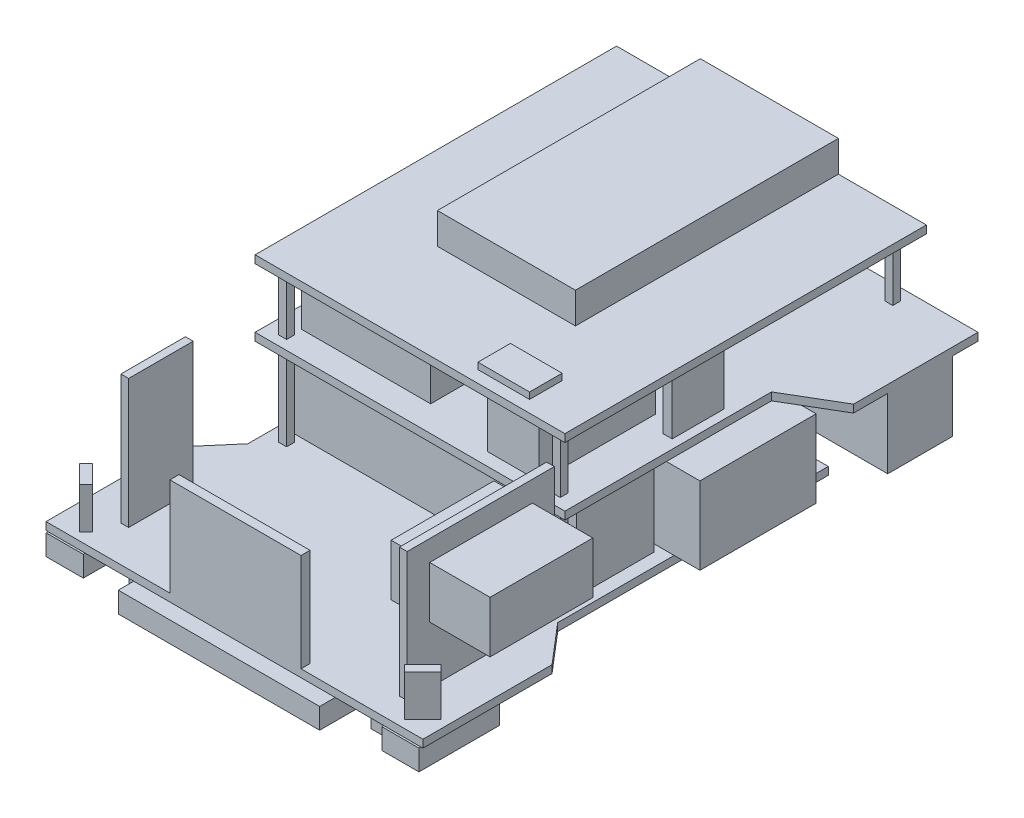
SolidWorks part; units mm, degrees
ref_plane "Front Plane" through (0, 0, 0) normal (0, 0, 1) x (1, 0, 0)
ref_plane "Top Plane" through (0, 0, 0) normal (0, 1, 0) x (1, 0, 0)
ref_plane "Right Plane" through (0, 0, 0) normal (1, 0, 0) x (0, 0, -1)
sketch "Sketch1" plane through (0, 0, 0) normal (0, 1, 0) x (1, 0, 0)
  line L0 (-73, -35) -> (-60, -19.8013)
  line L1 (60, -85) -> (-60, -85)
  line L2 (60, -19.8013) -> (60, 85)
  line L3 (60, 85) -> (-60, 85)
  line L4 (-60, -19.8013) -> (-60, 85)
  line L5 (60, -85) -> (-60, 85) construction
  line L6 (60, 85) -> (-60, -85) construction
  line L7 (0, 0) -> (0, -85) construction
  line L9 (-60, -85) -> (-73, -85)
  line L10 (-73, -35) -> (-73, -85)
  line L11 (60, -85) -> (73, -85)
  line L12 (73, -35) -> (73, -85)
  line L13 (73, -35) -> (60, -19.8013)
  point P0 (0, 0)
  dimension "D1" = 170
  dimension "D2" = 120
  dimension "D3" = 50
  dimension "D4" = 13
  dimension "D5" = 20
extrude "Boss-Extrude1" add sketch "Sketch1" along normal blind 3
sketch "Sketch2" plane through (0, 3, 0) normal (0, 1, 0) x (1, 0, 0)
  line L0 (0, 0) -> (0, 85) construction
  line L1 (60, 85) -> (-60, 85) construction
  line L2 (-60, 85) -> (-60, -19.8013) construction
  line L4 (-54.525, -13.335) -> (-51.475, -13.335)
  line L5 (-54.525, -13.335) -> (-54.525, -10.285)
  line L6 (-54.525, -10.285) -> (-51.475, -10.285)
  line L7 (-51.475, -13.335) -> (-51.475, -10.285)
  line L8 (-54.525, -13.335) -> (-51.475, -10.285) construction
  line L9 (-54.525, -10.285) -> (-51.475, -13.335) construction
  line L10 (51.475, -13.335) -> (54.525, -13.335)
  line L11 (51.475, -13.335) -> (51.475, -10.285)
  line L12 (51.475, -10.285) -> (54.525, -10.285)
  line L13 (54.525, -13.335) -> (54.525, -10.285)
  line L14 (51.475, -13.335) -> (54.525, -10.285) construction
  line L15 (51.475, -10.285) -> (54.525, -13.335) construction
  line L16 (52.475, 73.475) -> (55.525, 73.475)
  line L17 (52.475, 73.475) -> (52.475, 76.525)
  line L18 (52.475, 76.525) -> (55.525, 76.525)
  line L19 (55.525, 73.475) -> (55.525, 76.525)
  line L20 (52.475, 73.475) -> (55.525, 76.525) construction
  line L21 (52.475, 76.525) -> (55.525, 73.475) construction
  line L22 (-55.525, 73.475) -> (-52.475, 73.475)
  line L23 (-55.525, 73.475) -> (-55.525, 76.525)
  line L24 (-55.525, 76.525) -> (-52.475, 76.525)
  line L25 (-52.475, 73.475) -> (-52.475, 76.525)
  line L26 (-55.525, 73.475) -> (-52.475, 76.525) construction
  line L27 (-55.525, 76.525) -> (-52.475, 73.475) construction
  circle A0 centre (-53, -11.81) radius 1.525 construction
  circle A1 centre (-54, 75) radius 1.525 construction
  circle A2 centre (53, -11.81) radius 1.525 construction
  circle A3 centre (54, 75) radius 1.525 construction
  dimension "D1" = 10
  dimension "D2" = 3.05
  dimension "D3" = 6
  dimension "D4" = 3.05
  dimension "D5" = 7
  dimension "D6" = 86.81
extrude "Boss-Extrude2" add sketch "Sketch2" along normal blind 33
sketch "Sketch3" plane through (0, 36, 0) normal (0, 1, 0) x (1, 0, 0)
  line L0 (0, 52.99) -> (0, 122.99) construction
  line L1 (-60, -17.01) -> (60, -17.01)
  line L2 (-60, -17.01) -> (-60, 122.99)
  line L3 (-60, 122.99) -> (60, 122.99)
  line L4 (60, -17.01) -> (60, 122.99)
  line L5 (-60, -17.01) -> (60, 122.99) construction
  line L6 (-60, 122.99) -> (60, -17.01) construction
  line L7 (-60, 122.99) -> (-80, 122.99)
  line L8 (-80, 122.99) -> (-80, 74.7803)
  line L9 (-80, 74.7803) -> (-60, 62.99)
  line L10 (80, 74.7803) -> (60, 62.99)
  line L11 (80, 122.99) -> (80, 74.7803)
  line L12 (60, 122.99) -> (80, 122.99)
  line L14 (-54.525, -10.285) -> (-54.525, -13.335) construction
  point P0 (0, 52.99)
  point P19 (-54.525, -11.81)
  dimension "D1" = 120
  dimension "D2" = 140
  dimension "D3" = 60
  dimension "D4" = 30.52
  dimension "D5" = 20
  dimension "D6" = 5.2
extrude "Boss-Extrude3" add sketch "Sketch3" along normal blind 3 contours L8 L9 L2 L7 | L1 L4 L3 L2 | L12 L4 L10 L11 | L2 L1 L4 L3 region at (0, 36, -52.99) region at (-69.6368, 36, -95.8305) region at (69.6368, 36, -95.8305)
sketch "Sketch4" plane through (0, 39, 0) normal (0, 1, 0) x (1, 0, 0)
  line L0 (0, 0) -> (0, 32.3428) construction
  line L1 (-54.525, -13.335) -> (-51.475, -13.335)
  line L2 (-54.525, -13.335) -> (-54.525, -10.285)
  line L3 (-54.525, -10.285) -> (-51.475, -10.285)
  line L4 (-51.475, -13.335) -> (-51.475, -10.285)
  line L5 (-54.525, -13.335) -> (-51.475, -10.285) construction
  line L6 (-54.525, -10.285) -> (-51.475, -13.335) construction
  line L7 (-60, -17.01) -> (60, -17.01) construction
  line L8 (-60, -17.01) -> (-60, 62.99) construction
  line L9 (80, 122.99) -> (-80, 122.99) construction
  line L10 (-54.525, 115.465) -> (-51.475, 115.465)
  line L11 (-54.525, 115.465) -> (-54.525, 118.515)
  line L12 (-54.525, 118.515) -> (-51.475, 118.515)
  line L13 (-51.475, 115.465) -> (-51.475, 118.515)
  line L14 (-54.525, 115.465) -> (-51.475, 118.515) construction
  line L15 (-54.525, 118.515) -> (-51.475, 115.465) construction
  line L16 (54.525, -10.285) -> (51.475, -13.335) construction
  line L17 (54.525, -13.335) -> (51.475, -10.285) construction
  line L18 (51.475, -13.335) -> (51.475, -10.285)
  line L19 (54.525, -10.285) -> (51.475, -10.285)
  line L20 (54.525, -13.335) -> (54.525, -10.285)
  line L21 (54.525, -13.335) -> (51.475, -13.335)
  line L22 (54.525, 118.515) -> (51.475, 115.465) construction
  line L23 (54.525, 115.465) -> (51.475, 118.515) construction
  line L24 (51.475, 115.465) -> (51.475, 118.515)
  line L25 (54.525, 118.515) -> (51.475, 118.515)
  line L26 (54.525, 115.465) -> (54.525, 118.515)
  line L27 (54.525, 115.465) -> (51.475, 115.465)
  point P0 (-53, -11.81)
  point P12 (-53, 116.99)
  point P24 (53, -11.81)
  point P29 (53, 116.99)
  dimension "D1" = 3.05
  dimension "D2" = 5.2
  dimension "D3" = 7
  dimension "D4" = 6
extrude "Boss-Extrude4" add sketch "Sketch4" along normal blind 23
sketch "Sketch6" plane through (0, 62, 0) normal (0, 1, 0) x (1, 0, 0)
  line L0 (60, -17.01) -> (-60, -17.01)
  line L1 (60, -17.01) -> (60, 122.99)
  line L2 (-60, -17.01) -> (-60, 122.99)
  line L3 (60, 122.99) -> (-60, 122.99)
  line L4 (80, 122.99) -> (-80, 122.99) construction
extrude "Boss-Extrude5" add sketch "Sketch6" along normal blind 3
sketch "Sketch7" plane through (0, 36, 0) normal (0, -1, 0) x (1, 0, 0)
  line L0 (-80, -88.03) -> (-80, -113.03)
  line L1 (-80, -88.03) -> (-12, -88.03)
  line L2 (-80, -113.03) -> (-12, -113.03)
  line L3 (-12, -88.03) -> (-12, -113.03)
  line L4 (-80, -122.99) -> (-80, -74.7803) construction
  line L5 (0, 0) -> (0, -39.6137) construction
  line L6 (12, -88.03) -> (12, -113.03)
  line L7 (80, -113.03) -> (12, -113.03)
  line L8 (80, -88.03) -> (12, -88.03)
  line L9 (80, -88.03) -> (80, -113.03)
  line L10 (80, -122.99) -> (-80, -122.99) construction
  point P13 (-80, -100.53)
  dimension "D1" = 68
  dimension "D2" = 25
  dimension "D3" = 22.46
extrude "Boss-Extrude6" add sketch "Sketch7" along normal blind 27
sketch "Sketch9" plane through (0, 39, 0) normal (0, 1, 0) x (1, 0, 0)
  line L0 (-60, -17.01) -> (-60, 62.99) construction
  line L1 (-30.05, 55.88) -> (27.95, 55.88)
  line L2 (-30.05, 55.88) -> (-30.05, 115.88)
  line L3 (-30.05, 115.88) -> (27.95, 115.88)
  line L4 (27.95, 55.88) -> (27.95, 115.88)
  line L5 (-30.05, 55.88) -> (27.95, 115.88) construction
  line L6 (-30.05, 115.88) -> (27.95, 55.88) construction
  line L7 (80, 122.99) -> (-80, 122.99) construction
  line L8 (0, 0) -> (0, 23.7636) construction
  line L13 (-60, 122.99) -> (-60, -17.01) construction
  line L15 (-60, -17.01) -> (60, -17.01) construction
  line L16 (45, -12.01) -> (25, -12.01)
  line L17 (25, 32.99) -> (25, -12.01)
  line L18 (45, 32.99) -> (25, 32.99)
  line L19 (45, 32.99) -> (45, -12.01)
  line L20 (-60, -17.01) -> (60, -17.01) construction
  line L21 (-52, 22.99) -> (-2, 22.99)
  line L22 (-52, 22.99) -> (-52, -7.01)
  line L23 (-52, -7.01) -> (-2, -7.01)
  line L24 (-2, 22.99) -> (-2, -7.01)
  line L25 (-52, 22.99) -> (-2, -7.01) construction
  line L26 (-52, -7.01) -> (-2, 22.99) construction
  line L27 (60, -17.01) -> (60, 122.99) construction
  point P0 (-1.05, 85.88)
  point P23 (-27, 7.99)
  dimension "D1" = 58
  dimension "D2" = 29.95
  dimension "D3" = 60
  dimension "D4" = 7.11
  dimension "D5" = 8
  dimension "D6" = 5
  dimension "D7" = 15
  dimension "D8" = 20
  dimension "D9" = 10
  dimension "D10" = 50
  dimension "D11" = 30
  dimension "D12" = 45
extrude "Boss-Extrude7" add sketch "Sketch9" along normal blind 20
sketch "Sketch10" plane through (0, 65, 0) normal (0, 1, 0) x (1, 0, 0)
  line L0 (-27.54, 122.99) -> (25.92, 122.99)
  line L1 (-27.54, 122.99) -> (-27.54, 21.14)
  line L2 (25.92, 122.99) -> (25.92, 21.14)
  line L3 (-27.54, 21.14) -> (25.92, 21.14)
  line L4 (60, 122.99) -> (-60, 122.99) construction
  line L5 (-60, 122.99) -> (-60, -17.01) construction
  dimension "D1" = 32.46
  dimension "D2" = 53.46
  dimension "D3" = 101.85
extrude "Boss-Extrude8" add sketch "Sketch10" along normal blind 12
sketch "Sketch11" plane through (0, 3, 0) normal (0, 1, 0) x (1, 0, 0)
  line L1 (-55, 22.5437) -> (55, 22.5437)
  line L2 (-55, 22.5437) -> (-55, -7.4563)
  line L3 (-55, -7.4563) -> (55, -7.4563)
  line L4 (55, 22.5437) -> (55, -7.4563)
  line L5 (-55, 22.5437) -> (55, -7.4563) construction
  line L6 (-55, -7.4563) -> (55, 22.5437) construction
  point P0 (0, 7.5437)
  dimension "D1" = 110
  dimension "D2" = 30
extrude "Boss-Extrude9" add sketch "Sketch11" along normal blind 32
sketch "Sketch12" plane through (0, 3, 0) normal (0, 1, 0) x (1, 0, 0)
  line L1 (-70, 25.2932) -> (70, 25.2932)
  line L2 (-70, 25.2932) -> (-70, 70.2932)
  line L3 (-70, 70.2932) -> (70, 70.2932)
  line L4 (70, 25.2932) -> (70, 70.2932)
  line L5 (-70, 25.2932) -> (70, 70.2932) construction
  line L6 (-70, 70.2932) -> (70, 25.2932) construction
  point P0 (0, 47.7932)
  dimension "D1" = 140
  dimension "D2" = 45
extrude "Boss-Extrude10" add sketch "Sketch12" along normal blind 30
sketch "Sketch13" plane through (0, 65, 0) normal (0, 1, 0) x (1, 0, 0)
  line L0 (60, -17.01) -> (60, 122.99) construction
  line L1 (21.68, -12.39) -> (41.68, -12.39)
  line L2 (21.68, -12.39) -> (21.68, 0.21)
  line L3 (21.68, 0.21) -> (41.68, 0.21)
  line L4 (41.68, -12.39) -> (41.68, 0.21)
  line L5 (21.68, -12.39) -> (41.68, 0.21) construction
  line L6 (21.68, 0.21) -> (41.68, -12.39) construction
  line L7 (-60, -17.01) -> (60, -17.01) construction
  point P0 (31.68, -6.09)
  dimension "D1" = 20
  dimension "D2" = 12.6
  dimension "D3" = 18.32
  dimension "D4" = 4.62
extrude "Boss-Extrude11" add sketch "Sketch13" along normal blind 2.5
sketch "Sketch14" plane through (0, 39, 0) normal (0, 1, 0) x (1, 0, 0)
  line L0 (60, -17.01) -> (60, 122.99) construction
  line L1 (56.55, 47.99) -> (52.95, 47.99)
  line L2 (56.55, 47.99) -> (56.55, 27.99)
  line L3 (56.55, 27.99) -> (52.95, 27.99)
  line L4 (52.95, 47.99) -> (52.95, 27.99)
  line L5 (56.55, 47.99) -> (52.95, 27.99) construction
  line L6 (56.55, 27.99) -> (52.95, 47.99) construction
  line L7 (-60, -17.01) -> (60, -17.01) construction
  line L8 (0, 0) -> (0, 51.8866) construction
  line L9 (-56.55, 27.99) -> (-52.95, 47.99) construction
  line L10 (-56.55, 47.99) -> (-52.95, 27.99) construction
  line L11 (-52.95, 47.99) -> (-52.95, 27.99)
  line L12 (-56.55, 27.99) -> (-52.95, 27.99)
  line L13 (-56.55, 47.99) -> (-56.55, 27.99)
  line L14 (-56.55, 47.99) -> (-52.95, 47.99)
  point P0 (54.75, 37.99)
  point P16 (-54.75, 37.99)
  dimension "D1" = 3.45
  dimension "D2" = 7.05
  dimension "D3" = 20
  dimension "D4" = 45
extrude "Boss-Extrude12" add sketch "Sketch14" along normal blind 20
sketch "Sketch15" plane through (0, 3, 0) normal (0, 1, 0) x (1, 0, 0)
  line L6 (0, 0) -> (0, -32.3725) construction
  line L11 (62.9289, -82) -> (60.4541, -79.5251)
  line L12 (60.4541, -79.5251) -> (67.5251, -72.4541)
  line L13 (67.5251, -72.4541) -> (70, -74.9289)
  line L14 (70, -74.9289) -> (62.9289, -82)
  line L15 (-70, -74.9289) -> (-62.9289, -82)
  line L16 (-67.5251, -72.4541) -> (-70, -74.9289)
  line L17 (-60.4541, -79.5251) -> (-67.5251, -72.4541)
  line L18 (-62.9289, -82) -> (-60.4541, -79.5251)
  line L19 (-73, -85) -> (73, -85) construction
  line L20 (73, -85) -> (73, -35) construction
  dimension "D1" = 3.5
  dimension "D2" = 10
  dimension "D3" = 3
  dimension "D4" = 3
  dimension "D5" = 45
extrude "Boss-Extrude13" add sketch "Sketch15" along normal blind 16
sketch "Sketch16" plane through (0, 3, 0) normal (0, 1, 0) x (1, 0, 0)
  line L0 (73, -85) -> (73, -35) construction
  line L1 (54, -18.1) -> (57, -18.1)
  line L2 (54, -18.1) -> (54, -75.1)
  line L3 (54, -75.1) -> (57, -75.1)
  line L4 (57, -18.1) -> (57, -75.1)
  line L5 (-73, -85) -> (73, -85) construction
  line L6 (-73, -35) -> (-73, -85) construction
  line L7 (-58, -46) -> (-55, -46)
  line L8 (-58, -46) -> (-58, -71)
  line L9 (-58, -71) -> (-55, -71)
  line L10 (-55, -46) -> (-55, -71)
  dimension "D1" = 19
  dimension "D2" = 3
  dimension "D3" = 57
  dimension "D4" = 9.9
  dimension "D5" = 15
  dimension "D6" = 3
  dimension "D7" = 25
  dimension "D8" = 14
extrude "Boss-Extrude14" add sketch "Sketch16" along normal blind 50
sketch "Sketch17" plane through (57, 0, 0) normal (1, 0, 0) x (0, 0, -1)
  line L0 (-75.1, 53) -> (-18.1, 53) construction
  line L1 (-66.4113, 45) -> (-26.6028, 45)
  line L2 (-66.4113, 45) -> (-66.4113, 25)
  line L3 (-66.4113, 25) -> (-26.6028, 25)
  line L4 (-26.6028, 45) -> (-26.6028, 25)
  dimension "D1" = 8
  dimension "D2" = 20
extrude "Boss-Extrude15" add sketch "Sketch17" along normal blind 23.4 and the other way blind 14.9
sketch "Sketch18" plane through (0, 0, 0) normal (0, -1, 0) x (1, 0, 0)
  line L0 (-73, 85) -> (73, 85) construction
  line L1 (-39, 66) -> (39, 66)
  line L2 (-39, 66) -> (-39, 91)
  line L3 (-39, 91) -> (39, 91)
  line L4 (39, 66) -> (39, 91)
  line L5 (0, 85) -> (0, 37.8257) construction
  line L6 (-72.2, 85.75) -> (-57.8, 85.75)
  line L7 (-72.2, 85.75) -> (-72.2, 54.45)
  line L8 (-72.2, 54.45) -> (-57.8, 54.45)
  line L9 (-57.8, 85.75) -> (-57.8, 54.45)
  line L10 (57.8, 85.75) -> (57.8, 54.45)
  line L11 (72.2, 54.45) -> (57.8, 54.45)
  line L12 (72.2, 85.75) -> (72.2, 54.45)
  line L13 (72.2, 85.75) -> (57.8, 85.75)
  line L14 (-73, 35) -> (-73, 85) construction
  point P4 (0, 66)
  dimension "D1" = 25
  dimension "D2" = 78
  dimension "D3" = 6
  dimension "D4" = 14.4
  dimension "D5" = 31.3
  dimension "D6" = 0.8
  dimension "D7" = 0.75
extrude "Boss-Extrude16" add sketch "Sketch18" along normal blind 8
sketch "Sketch20" plane through (0, 0, 0) normal (0, -1, 0) x (1, 0, 0)
  line L0 (0, 0) -> (0, 27.2161) construction
  line L1 (-51.89, 74) -> (-41.89, 74)
  line L2 (-51.89, 74) -> (-51.89, 64)
  line L3 (-51.89, 64) -> (-41.89, 64)
  line L4 (-41.89, 74) -> (-41.89, 64)
  line L9 (41.89, 74) -> (41.89, 64)
  line L10 (51.89, 64) -> (41.89, 64)
  line L11 (51.89, 74) -> (51.89, 64)
  line L12 (51.89, 74) -> (41.89, 74)
  line L14 (80, -88.03) -> (80, -74.7803) construction
  line L15 (39, 85) -> (57.8, 85) construction
  dimension "D1" = 10
  dimension "D2" = 10
  dimension "D3" = 11
  dimension "D4" = 28.11
extrude "Boss-Extrude18" add sketch "Sketch20" along normal blind 14.56
sketch "Sketch21" plane through (0, -14.56, 0) normal (0, -1, 0) x (1, 0, 0)
  line L14 (50.89, 65) -> (50.89, 73)
  line L15 (42.89, 65) -> (50.89, 65)
  line L16 (42.89, 73) -> (42.89, 65)
  line L17 (50.89, 73) -> (42.89, 73)
  line L18 (50.89, 65) -> (50.89, 73)
  line L19 (42.89, 65) -> (50.89, 65)
  line L20 (42.89, 73) -> (42.89, 65)
  line L21 (50.89, 73) -> (42.89, 73)
  line L32 (-42.89, 65) -> (-42.89, 73)
  line L33 (-50.89, 65) -> (-42.89, 65)
  line L34 (-50.89, 73) -> (-50.89, 65)
  line L35 (-42.89, 73) -> (-50.89, 73)
  line L36 (-42.89, 65) -> (-42.89, 73)
  line L37 (-50.89, 65) -> (-42.89, 65)
  line L38 (-50.89, 73) -> (-50.89, 65)
  line L39 (-42.89, 73) -> (-50.89, 73)
  dimension "D1" = 1
  dimension "D2" = 1
extrude "Cut-Extrude1" cut sketch "Sketch21" against normal blind 5
sketch "Sketch22" plane through (0, 3, 0) normal (0, 1, 0) x (1, 0, 0)
  line L0 (-73, -35) -> (-73, -85) construction
  line L1 (-25, -81.5) -> (25.76, -81.5)
  line L2 (-25, -81.5) -> (-25, -85)
  line L3 (-25, -85) -> (25.76, -85)
  line L4 (25.76, -81.5) -> (25.76, -85)
  line L5 (73, -85) -> (73, -35) construction
  line L6 (-39, -85) -> (39, -85) construction
  dimension "D1" = 48
  dimension "D2" = 47.24
  dimension "D3" = 3.5
extrude "Boss-Extrude19" add sketch "Sketch22" along normal blind 38
